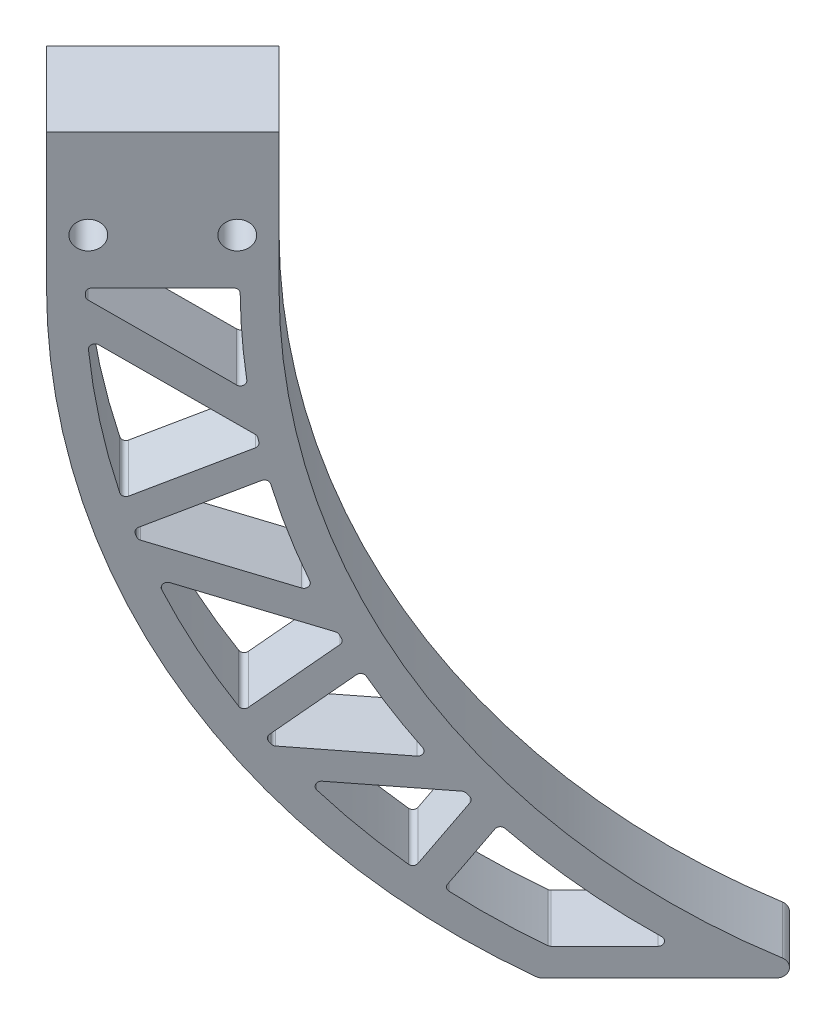
SolidWorks part; units mm, degrees
ref_plane "Front Plane" through (0, 0, 0) normal (0, 0, 1) x (1, 0, 0)
ref_plane "Top Plane" through (0, 0, 0) normal (0, 1, 0) x (1, 0, 0)
ref_plane "Right Plane" through (0, 0, 0) normal (1, 0, 0) x (0, 0, -1)
ref_plane "Plane1" through (50.5423, 0, -50.5423) normal (-0.7071, 0, 0.7071) x (0.7071, 0, 0.7071)
ref_plane "Plane2" through (61.1489, 0, -61.1489) normal (-0.7071, 0, 0.7071) x (0.7071, 0, 0.7071)
sketch "Sketch1" plane through (61.1489, 0, -61.1489) normal (-0.7071, 0, 0.7071) x (0.7071, 0, 0.7071)
  line L0 (-8, -81.9015) -> (-8, -78.9015) construction
  line L1 (-8, -78.9015) -> (4, -78.9015) construction
  line L2 (4, -78.9015) -> (4, -92.9015) construction
  line L3 (-4, -84.2109) -> (-8, -81.9015) construction
  line L4 (-4, -92.9015) -> (-4, -84.2109) construction
  line L5 (-8, -81.9015) -> (-8, -78.9015) construction
  line L6 (-8, -78.9015) -> (4, -78.9015) construction
  line L7 (4, -78.9015) -> (4, -92.9015) construction
  line L8 (-4, -84.2109) -> (-8, -81.9015) construction
  line L9 (-4, -92.9015) -> (-4, -84.2109) construction
  line L10 (-3.75, -92.9015) -> (-3.75, -84.0666)
  line L11 (-3.75, -84.0666) -> (-7.75, -81.7572)
  line L12 (-7.75, -81.7572) -> (-7.75, -79.1515)
  line L13 (-7.75, -79.1515) -> (3.75, -79.1515)
  line L14 (3.75, -79.1515) -> (3.75, -92.9015)
  line L15 (-3.75, -92.9015) -> (-3.75, -159.1515)
  line L16 (3.75, -92.9015) -> (3.75, -159.1515)
  line L17 (3.75, -159.1515) -> (-3.75, -159.1515)
  dimension "D2" = 80
  dimension "D1" = 0.25
extrude "Boss-Extrude1" add sketch "Sketch1" along normal blind 40 and the other way blind 40
sketch "Sketch2" plane through (-2.6517, 0, -2.6517) normal (-0.7071, 0, -0.7071) x (-0.7071, 0, 0.7071)
  line L0 (-83.5847, -79.1515) -> (-83.5847, -93.9015)
  line L1 (-126.4776, -79.1515) -> (-46.4776, -79.1515) construction
  line L2 (-83.5847, -78.9015) -> (-83.5847, -81.9015) construction
  line L6 (-83.8177, -93.9015) -> (-83.3691, -93.9015) construction
  line L7 (-65.6347, -93.9015) -> (-65.6347, -79.1515)
  line L10 (-126.4776, -159.1515) -> (-46.4776, -159.1515) construction
  line L11 (-126.4776, -159.1515) -> (-126.4776, -79.1515)
  line L12 (-126.4776, -79.1515) -> (-83.5847, -79.1515)
  line L13 (-65.6347, -79.1515) -> (-46.4776, -79.1515)
  line L14 (-46.4776, -79.1515) -> (-46.4776, -159.1515)
  line L15 (-46.4776, -159.1515) -> (-103.6558, -159.1515)
  arc A0 (-83.5847, -93.9015) -> (-126.4776, -159.1515) centre (-154.6613, -93.9015) cw
  arc A1 (-65.6347, -93.9015) -> (-103.6558, -159.1515) centre (-140.6347, -93.9015) cw
  dimension "D1" = 75
  dimension "D2" = 17.95
extrude "Cut-Extrude1" cut sketch "Sketch2" against normal through all and the other way blind 30
sketch "Sketch3" plane through (2.6517, 0, 2.6517) normal (0.7071, 0, 0.7071) x (0.7071, 0, -0.7071)
  line L0 (83.5847, -79.1515) -> (65.6347, -79.1515) construction
  line L1 (68.8597, -88.9015) -> (80.3597, -88.9015) construction
  line L2 (74.6097, -88.9015) -> (74.6097, -79.1515) construction
  circle A0 centre (68.8597, -88.9015) radius 1.5
  circle A1 centre (80.3597, -88.9015) radius 1.5
  point P6 (0, 0)
  point P7 (80.3409, -87.9734)
  dimension "D1" = 3
  dimension "D2" = 11.5
  dimension "D3" = 9.75
extrude "Cut-Extrude2" cut sketch "Sketch3" against normal through all
fillet "Fillet1" radius 1 2 edges at (73.2957, -159.1515, -73.2957) (89.4331, -159.1515, -89.4331)
sketch "Sketch4" plane through (-2.6517, 0, -2.6517) normal (-0.7071, 0, -0.7071) x (-0.7071, 0, 0.7071)
  line L1 (-68.6347, -93.9015) -> (-80.5847, -93.9015)
  line L2 (-104.4555, -156.1515) -> (-114.5081, -156.1515)
  line L3 (-104.4555, -156.1515) -> (-114.5081, -156.1515) construction
  line L4 (-68.6416, -94.9015) -> (-81.2385, -103.722)
  line L5 (-81.9107, -107.855) -> (-68.7928, -98.6696)
  line L6 (-82.1097, -108.855) -> (-71.4468, -113.8272)
  line L7 (-82.7913, -111.8472) -> (-72.3456, -116.7182)
  line L8 (-72.6691, -117.6644) -> (-86.3951, -122.6602)
  line L9 (-74.0806, -121.3707) -> (-88.1364, -126.4866)
  line L10 (-88.5824, -127.3817) -> (-80.784, -133.9252)
  line L11 (-90.0246, -130.0877) -> (-82.5101, -136.3931)
  line L12 (-83.1059, -137.1963) -> (-95.3394, -138.2666)
  line L13 (-114.5081, -156.1515) -> (-104.4555, -156.1515)
  line L14 (-97.903, -141.5023) -> (-85.6917, -140.434)
  line L15 (-98.5507, -142.2642) -> (-94.0024, -148.7598)
  line L16 (-100.6093, -144.5545) -> (-96.3344, -150.6597)
  line L17 (-104.4555, -156.1515) -> (-101.2356, -156.1926)
  arc A4 (-80.5847, -93.9015) -> (-81.2385, -103.722) centre (-154.6615, -93.9015) cw
  arc A5 (-68.6347, -93.9015) -> (-68.6416, -94.9015) centre (-140.6347, -93.9015) cw
  arc A6 (-81.9107, -107.855) -> (-82.1097, -108.855) centre (-154.6613, -93.9015) cw
  arc A7 (-68.7928, -98.6696) -> (-71.4468, -113.8272) centre (-140.6347, -93.9015) cw
  arc A8 (-104.4555, -156.1515) -> (-68.6347, -93.9015) centre (-140.6347, -93.9015) ccw
  arc A9 (-114.5081, -156.1515) -> (-80.5847, -93.9015) centre (-154.6613, -93.9015) ccw
  arc A10 (-104.4555, -156.1515) -> (-96.3344, -150.6597) centre (-140.6347, -93.9015) ccw construction
  arc A11 (-114.5081, -156.1515) -> (-100.6093, -144.5545) centre (-154.6613, -93.9015) ccw construction
  arc A12 (-72.3456, -116.7182) -> (-72.6691, -117.6644) centre (-140.6347, -93.9015) cw
  arc A13 (-82.7913, -111.8472) -> (-86.3951, -122.6602) centre (-154.6613, -93.9015) cw
  arc A14 (-86.3951, -122.6602) -> (-80.5847, -93.9015) centre (-154.6613, -93.9015) ccw construction
  arc A15 (-88.1364, -126.4866) -> (-95.3394, -138.2666) centre (-154.6613, -93.9015) cw
  arc A16 (-72.6691, -117.6644) -> (-68.6347, -93.9015) centre (-140.6347, -93.9015) ccw construction
  arc A17 (-74.0806, -121.3707) -> (-83.1059, -137.1963) centre (-140.6347, -93.9015) cw
  arc A18 (-95.3394, -138.2666) -> (-88.1364, -126.4866) centre (-154.6613, -93.9015) ccw construction
  arc A19 (-97.903, -141.5023) -> (-98.5507, -142.2642) centre (-154.6613, -93.9015) cw
  arc A20 (-83.1059, -137.1963) -> (-74.0806, -121.3707) centre (-140.6347, -93.9015) ccw construction
  arc A21 (-85.6917, -140.434) -> (-94.0024, -148.7598) centre (-140.6347, -93.9015) cw
  arc A22 (-98.5507, -142.2642) -> (-97.903, -141.5023) centre (-154.6613, -93.9015) ccw construction
  arc A23 (-100.6093, -144.5545) -> (-114.5081, -156.1515) centre (-154.6613, -93.9015) cw
  arc A24 (-94.0024, -148.7598) -> (-85.6917, -140.434) centre (-140.6347, -93.9015) ccw construction
  arc A25 (-96.3344, -150.6597) -> (-104.4555, -156.1515) centre (-140.6347, -93.9015) cw
  dimension "D2" = 3
  dimension "D3" = 3
  dimension "D4" = 3
  dimension "D5" = 3
  dimension "D6" = 3
  dimension "D7" = 1
  dimension "D8" = 1
  dimension "D9" = 35
  dimension "D10" = 60
  dimension "D11" = 45
  dimension "D12" = 1
  dimension "D13" = 1
  dimension "D14" = 60
  dimension "D15" = 1
  dimension "D16" = 45
  dimension "D17" = 1
  dimension "D18" = 3
  dimension "D19" = 60
  dimension "D1" = 3
extrude "Cut-Extrude3" cut sketch "Sketch4" against normal blind 40 contours A25 L16 A23 L13 | A21 L14 A19 L15 | A17 L11 A15 L12 | A17 L9 A15 L10 | L7 A13 L8 A12 | A7 L5 A6 L6 | A5 L1 A4 L4 region at (51.3436, -97.1801, -56.6469) region at (49.7717, -106.9652, -55.075) region at (54.0139, -117.2294, -59.3172) region at (54.7272, -127.4049, -60.0305) region at (60.2917, -135.1435, -65.595) region at (62.9311, -143.6501, -68.2344) region at (70.8176, -151.6831, -76.1209)
fillet "Fillet2" radius 0.5 28 edges at (80.9694, -156.1515, -80.9694) (71.1415, -144.5545, -71.1415) (68.1187, -150.6597, -68.1187) (73.8612, -156.1515, -73.8612) (66.4697, -148.7598, -66.4697) (60.5932, -140.434, -60.5932) (69.2279, -141.5023, -69.2279) (69.6859, -142.2642, -69.6859) (67.4151, -138.2666, -67.4151) (63.657, -130.0877, -63.657) (58.3435, -136.3931, -58.3435) (58.7647, -137.1963, -58.7647) (57.1229, -133.9252, -57.1229) (52.3829, -121.3707, -52.3829) (62.3219, -126.4866, -62.3219) (62.6372, -127.3817, -62.6372) (61.0905, -122.6602, -61.0905) (58.5423, -111.8472, -58.5423) (51.1561, -116.7182, -51.1561) (51.3848, -117.6644, -51.3848) (50.5205, -113.8272, -50.5205) (48.6438, -98.6696, -48.6438) (57.9196, -107.855, -57.9196) (58.0603, -108.855, -58.0603) (57.4443, -103.722, -57.4443) (56.982, -93.9015, -56.982) (48.537, -94.9015, -48.537) (48.5321, -93.9015, -48.5321)
